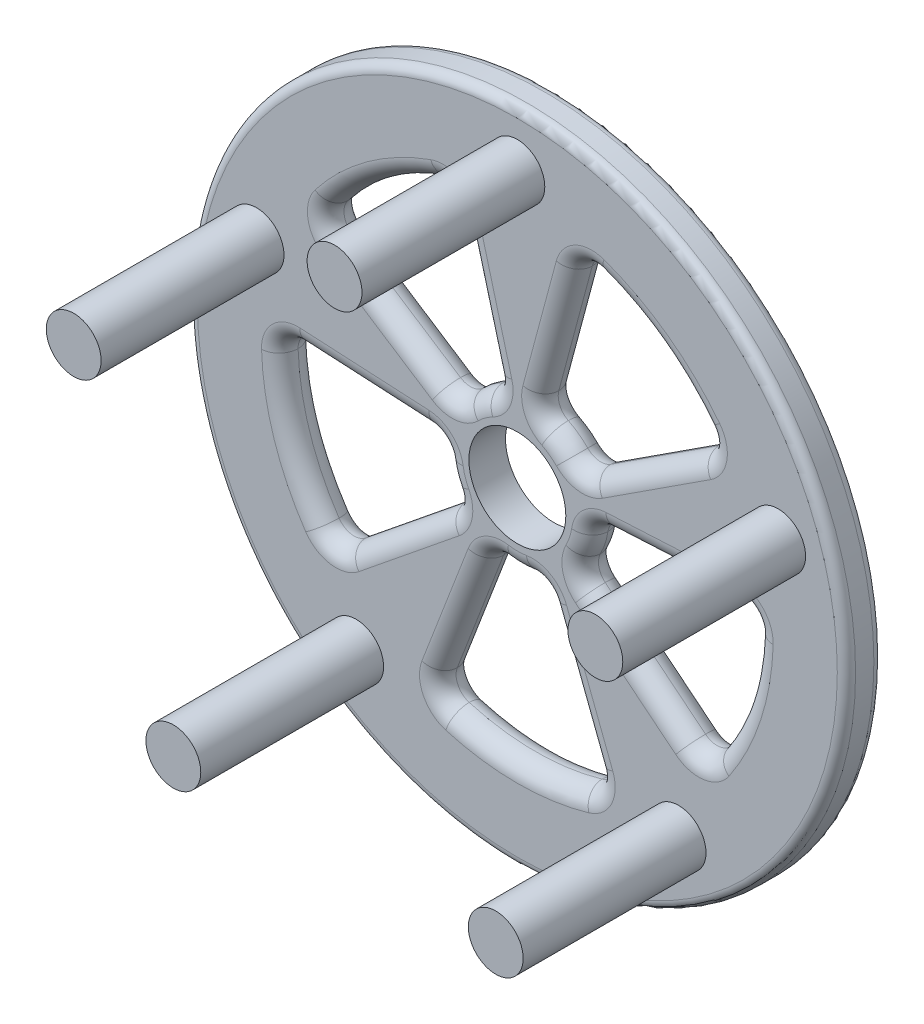
SolidWorks part; units mm, degrees
ref_plane "Front Plane" through (0, 0, 0) normal (0, 0, 1) x (1, 0, 0)
ref_plane "Top Plane" through (0, 0, 0) normal (0, 1, 0) x (1, 0, 0)
ref_plane "Right Plane" through (0, 0, 0) normal (1, 0, 0) x (0, 0, -1)
sketch "Sketch1" plane through (0, 0, 0) normal (0, 0, 1) x (1, 0, 0)
  line L0 (-1.0353, 3.8637) -> (-3.3646, 12.557)
  line L1 (1.0353, 3.8637) -> (3.3646, 12.557)
  line L2 (3.9945, 0.2093) -> (12.9822, 0.6804)
  line L3 (3.3547, 2.1786) -> (10.9027, 7.0803)
  line L4 (1.4335, -3.7343) -> (4.6588, -12.1365)
  line L5 (3.1086, -2.5173) -> (10.1029, -8.1812)
  line L6 (-3.1086, -2.5173) -> (-10.1029, -8.1812)
  line L7 (-1.4335, -3.7343) -> (-4.6588, -12.1365)
  line L8 (-3.3547, 2.1786) -> (-10.9027, 7.0803)
  line L9 (-3.9945, 0.2093) -> (-12.9822, 0.6804)
  circle A0 centre (0, 0) radius 18
  arc A1 (-12.9822, 0.6804) -> (-10.1029, -8.1812) centre (0, 0) ccw
  arc A2 (-1.4335, -3.7343) -> (1.4335, -3.7343) centre (0, 0) ccw
  arc A3 (-3.3646, 12.557) -> (3.3646, 12.557) centre (0, 0) cw construction
  arc A4 (-1.0353, 3.8637) -> (1.0353, 3.8637) centre (0, 0) cw construction
  arc A5 (3.3547, 2.1786) -> (3.9945, 0.2093) centre (0, 0) cw construction
  arc A6 (10.9027, 7.0803) -> (12.9822, 0.6804) centre (0, 0) cw construction
  arc A7 (3.1086, -2.5173) -> (1.4335, -3.7343) centre (0, 0) cw construction
  arc A8 (10.1029, -8.1812) -> (4.6588, -12.1365) centre (0, 0) cw construction
  arc A9 (-1.4335, -3.7343) -> (-3.1086, -2.5173) centre (0, 0) cw construction
  arc A10 (-4.6588, -12.1365) -> (-10.1029, -8.1812) centre (0, 0) cw construction
  arc A11 (-3.9945, 0.2093) -> (-3.3547, 2.1786) centre (0, 0) cw construction
  arc A12 (-12.9822, 0.6804) -> (-10.9027, 7.0803) centre (0, 0) cw construction
  arc A13 (-10.9027, 7.0803) -> (-12.9822, 0.6804) centre (0, 0) ccw construction
  arc A14 (3.3646, 12.557) -> (-3.3646, 12.557) centre (0, 0) ccw construction
  arc A15 (-3.3646, 12.557) -> (-10.9027, 7.0803) centre (0, 0) ccw
  arc A16 (12.9822, 0.6804) -> (10.9027, 7.0803) centre (0, 0) ccw construction
  arc A17 (10.9027, 7.0803) -> (3.3646, 12.557) centre (0, 0) ccw
  arc A18 (4.6588, -12.1365) -> (10.1029, -8.1812) centre (0, 0) ccw construction
  arc A19 (10.1029, -8.1812) -> (12.9822, 0.6804) centre (0, 0) ccw
  arc A20 (-10.1029, -8.1812) -> (-4.6588, -12.1365) centre (0, 0) ccw construction
  arc A21 (-4.6588, -12.1365) -> (4.6588, -12.1365) centre (0, 0) ccw
  arc A22 (-3.1086, -2.5173) -> (-1.4335, -3.7343) centre (0, 0) ccw construction
  arc A23 (-3.3547, 2.1786) -> (-3.9945, 0.2093) centre (0, 0) ccw construction
  arc A24 (-3.9945, 0.2093) -> (-3.1086, -2.5173) centre (0, 0) ccw
  arc A25 (1.0353, 3.8637) -> (-1.0353, 3.8637) centre (0, 0) ccw construction
  arc A26 (-1.0353, 3.8637) -> (-3.3547, 2.1786) centre (0, 0) ccw
  arc A27 (3.9945, 0.2093) -> (3.3547, 2.1786) centre (0, 0) ccw construction
  arc A28 (3.3547, 2.1786) -> (1.0353, 3.8637) centre (0, 0) ccw
  arc A29 (1.4335, -3.7343) -> (3.1086, -2.5173) centre (0, 0) ccw construction
  arc A30 (3.1086, -2.5173) -> (3.9945, 0.2093) centre (0, 0) ccw
  point P29 (0, 0)
  dimension "D1" = 36
  dimension "D2" = 26
  dimension "D3" = 8
  dimension "D4" = 30
  dimension "D5" = 30
  dimension "D6" = 5
extrude "Boss-Extrude1" add sketch "Sketch1" along normal blind 2 contours A0 A21 L7 A2 L4 L9 A24 L6 A1 L0 A26 L8 A15 L3 A28 L1 A17 L5 A30 L2 A19
fillet "Fillet1" radius 1 40 edges at (7.6412, 10.5172, 2) (7.6412, 10.5172, 0) (2.2, 8.2104, 2) (2.2, 8.2104, 0) (7.1287, 4.6294, 2) (7.1287, 4.6294, 0) (6.6057, -5.3492, 2) (6.6057, -5.3492, 0) (3.8042, -1.2361, 2) (3.8042, -1.2361, 0) (2.3511, 3.2361, 2) (2.3511, 3.2361, 0) (0, -13, 2) (0, -13, 0) (-3.0461, -7.9354, 2) (-3.0461, -7.9354, 0) (0, -4, 2) (0, -4, 0) (3.0461, -7.9354, 2) (3.0461, -7.9354, 0) (12.3637, -4.0172, 2) (12.3637, -4.0172, 0) (8.4884, 0.4449, 2) (8.4884, 0.4449, 0) (-6.6057, -5.3492, 2) (-6.6057, -5.3492, 0) (-12.3637, -4.0172, 2) (-12.3637, -4.0172, 0) (-8.4884, 0.4449, 2) (-8.4884, 0.4449, 0) (-3.8042, -1.2361, 2) (-3.8042, -1.2361, 0) (-2.3511, 3.2361, 2) (-2.3511, 3.2361, 0) (-2.2, 8.2104, 2) (-2.2, 8.2104, 0) (-7.6412, 10.5172, 2) (-7.6412, 10.5172, 0) (-7.1287, 4.6294, 2) (-7.1287, 4.6294, 0)
fillet "Fillet2" radius 0.5 2 edges at (18, 0, 0) (18, 0, 2)
sketch "Sketch2" plane through (0, 0, 2) normal (0, 0, 1) x (1, 0, 0)
  circle A0 centre (0, 0) radius 15 construction
  circle A1 centre (0, 15) radius 1.5
  circle A2 centre (14.2658, 4.6353) radius 1.5
  circle A3 centre (8.8168, -12.1353) radius 1.5
  circle A4 centre (-8.8168, -12.1353) radius 1.5
  circle A5 centre (-14.2658, 4.6353) radius 1.5
  point P15 (0, 0)
  dimension "D1" = 30
  dimension "D2" = 3
  dimension "D3" = 5
extrude "Boss-Extrude2" add sketch "Sketch2" along normal blind 10
sketch "Sketch3" plane through (0, 0, 2) normal (0, 0, 1) x (1, 0, 0)
  point P0 (0, 0)
sketch "Sketch4" plane through (0, 0, 0) normal (0, 0, -1) x (-1, 0, 0)
  circle A0 centre (0, 0) radius 2.65
  dimension "D1" = 5.3
extrude "Cut-Extrude1" cut sketch "Sketch4" against normal up to surface (2 mm away) up to face at (-12.7658, 4.6353, 2)
